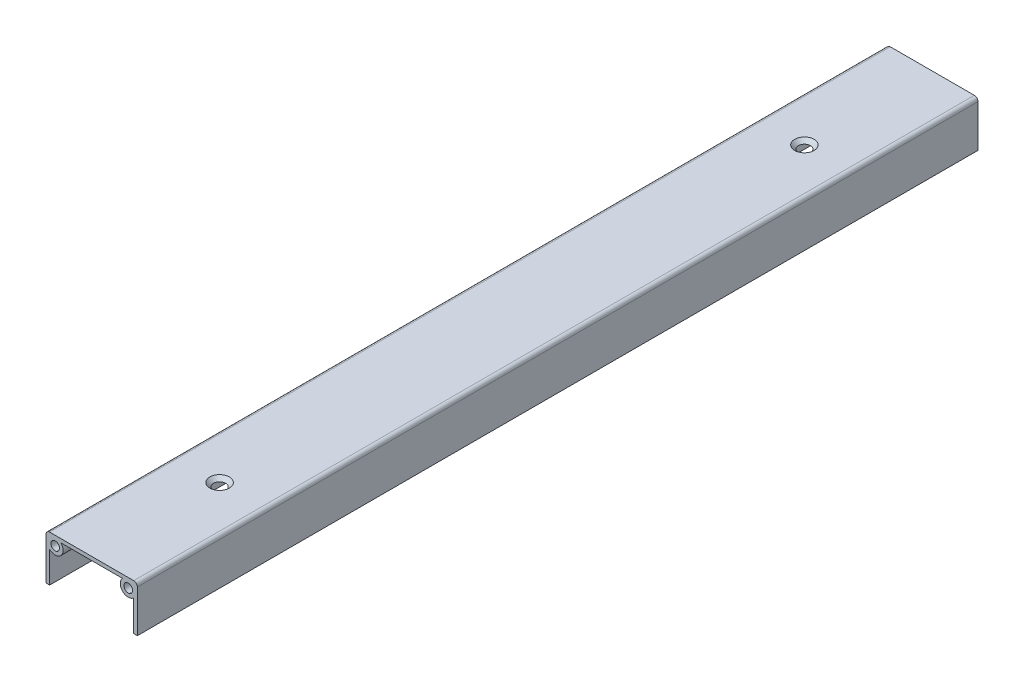
SolidWorks part; units mm, degrees
ref_plane "Front Plane" through (0, 0, 0) normal (0, 0, 1) x (1, 0, 0)
ref_plane "Top Plane" through (0, 0, 0) normal (0, 1, 0) x (1, 0, 0)
ref_plane "Right Plane" through (0, 0, 0) normal (1, 0, 0) x (0, 0, -1)
sketch "Sketch1" plane through (0, 0, 0) normal (0, 0, 1) x (1, 0, 0)
  line L0 (0, 31.75) -> (0, -31.75) construction
  line L1 (-31.75, -31.75) -> (31.75, -31.75)
  line L2 (-31.75, -31.75) -> (-31.75, 31.75)
  line L3 (-31.75, 31.75) -> (31.75, 31.75)
  line L4 (31.75, -31.75) -> (31.75, 31.75)
  line L5 (-31.75, -31.75) -> (31.75, 31.75) construction
  line L6 (-31.75, 31.75) -> (31.75, -31.75) construction
  line L7 (-31.75, 0) -> (31.75, 0) construction
  circle A0 centre (-25.4, 25.4) radius 3
  circle A1 centre (25.4, -25.4) radius 3
  circle A2 centre (-25.4, -25.4) radius 3
  circle A3 centre (25.4, 25.4) radius 3
  point P0 (0, 0)
  dimension "D3" = 6
  dimension "D9" = 50.8
  dimension "D4" = 50.8
  dimension "D1" = 63.5
  dimension "D2" = 63.5
  dimension "D5" = 6.35
extrude "Boss-Extrude1" add sketch "Sketch1" along normal mid plane 584.2
fillet "Fillet1" radius 2.54 4 edges at (-31.75, -31.75, 0) (31.75, -31.75, 0) (-31.75, 31.75, 0) (31.75, 31.75, 0)
shell "Shell1" thickness 2.54 removed face at (-28.4, -25.4, -292.1) removed face at (0, 0, 292.1)
sketch "Sketch3" plane through (0, 0, 292.1) normal (0, 0, 1) x (1, 0, 0)
  line L1 (-31.75, 29.21) -> (-31.75, -29.21) construction
  line L2 (-31.75, -0.1289) -> (31.9153, -0.1289)
  line L3 (-31.75, -0.1289) -> (-31.75, -31.8789)
  line L4 (-31.75, -31.8789) -> (31.9153, -31.8789)
  line L5 (31.9153, -0.1289) -> (31.9153, -31.8789)
  dimension "D1" = 31.75
extrude "Cut-Extrude2" cut sketch "Sketch3" against normal through all
hole_wizard "CSK for M6 Hex Socket Countersunk Head Screw1" positions "Sketch9" profile "Sketch8" countersink size "M6" standard "Lanco STD" end condition through all
sketch "Sketch9" plane through (0, 31.75, 0) normal (0, 1, 0) x (1, 0, 0)
  line L0 (29.21, -292.1) -> (-29.21, -292.1) construction
  line L1 (21.3781, 292.1) -> (-21.3781, 292.1) construction
  point P0 (0, 203.2)
  point P2 (0, -203.2)
  point P7 (0, 292.1)
  dimension "D1" = 88.9
  dimension "D2" = 88.9
sketch "Sketch8" plane through (0, 31.75, -203.2) normal (1, 0, 0) x (0, 0, 1)
  line L0 (0, 0) -> (0, 31.8789)
  line L1 (0, 31.8789) -> (3.2, 31.8789)
  line L2 (3.2, 31.8789) -> (3.2, 3.55)
  line L3 (3.2, 3.55) -> (6.75, 0)
  line L5 (6.75, 0) -> (0, 0)
  line L6 (-3.2, 3.55) -> (-6.75, 0) construction
  line L11 (0, -6.35) -> (0, 107.95) construction
  dimension "Thru Hole Dia." = 6.4
  dimension "Thru Hole Depth" = 31.8789
  dimension "Near C'Sink Dia." = 13.5
  dimension "Near C'Sink Angle" = 90
equation "\"D1@Boss-Extrude1\" = \"robot_width@2016 Chassis 3.0.Assembly\" - 6in"
